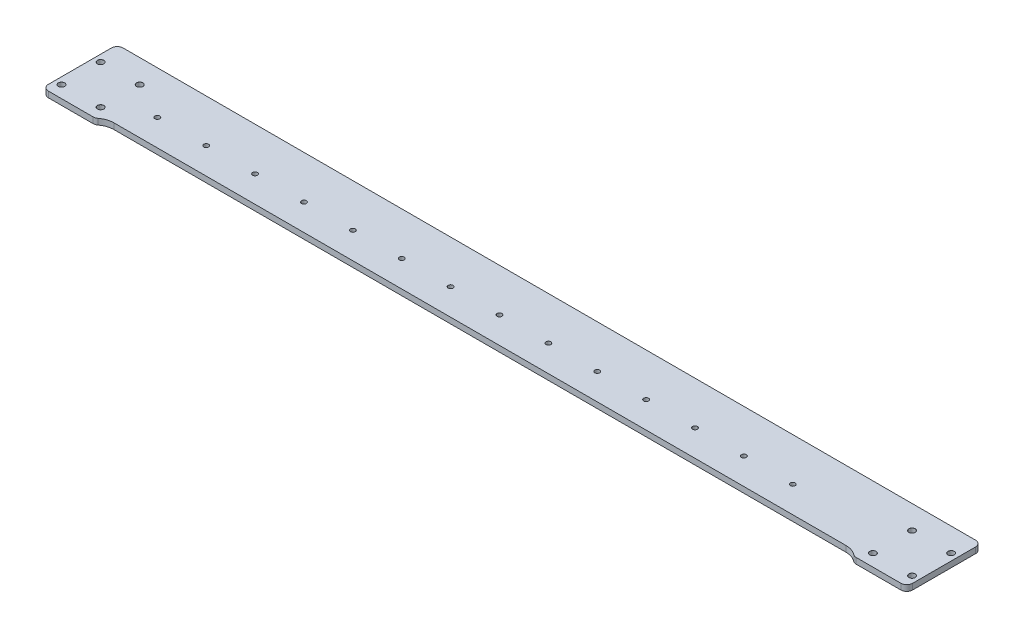
SolidWorks part; units mm, degrees
material "AISI 1045 Steel, cold drawn"
ref_plane "Front Plane" through (0, 0, 0) normal (0, 0, 1) x (1, 0, 0)
ref_plane "Top Plane" through (0, 0, 0) normal (0, 1, 0) x (1, 0, 0)
ref_plane "Right Plane" through (0, 0, 0) normal (1, 0, 0) x (0, 0, -1)
sketch "Sketch1" plane through (0, 0, 0) normal (0, 1, 0) x (1, 0, 0)
  line L0 (0, 0) -> (194, 0)
  line L1 (194, 0) -> (194, -2.7)
  line L2 (194, -2.7) -> (221, -2.7)
  line L3 (221, -2.7) -> (221, 29.7)
  line L4 (221, 29.7) -> (0, 29.7) construction
  line L7 (0, 0) -> (0, 29.7)
  line L8 (221, 13.5) -> (0, 13.5) construction
  line L9 (221, 29.7) -> (221, 35.5)
  line L10 (221, 35.5) -> (0, 35.5)
  line L11 (0, 35.5) -> (0, 29.7)
  dimension "D1" = 194
  dimension "D2" = 27
  dimension "D3" = 29.7
  dimension "D4" = 32.4
  dimension "D5" = 22
extrude "Boss-Extrude1" add sketch "Sketch1" along normal blind 3
hole_wizard "M3 Clearance Hole1" positions "Sketch2" profile "Sketch3" hole size "M3" standard "ANSI Metric" end condition through all
sketch "Sketch2" plane through (0, 3, 0) normal (0, 1, 0) x (1, 0, 0)
  line L1 (217.5, 3.5) -> (197.5, 3.5)
  line L2 (217.5, 3.5) -> (217.5, 23.5)
  line L3 (217.5, 23.5) -> (197.5, 23.5)
  line L4 (197.5, 3.5) -> (197.5, 23.5)
  line L5 (217.5, 3.5) -> (197.5, 23.5) construction
  line L6 (217.5, 23.5) -> (197.5, 3.5) construction
  line L10 (207.5, 13.5) -> (207.5, -2.7) construction
  line L13 (194, -2.7) -> (221, -2.7) construction
  line L17 (0, 0) -> (194, 0) construction
  point P2 (197.5, 23.5)
  point P35 (217.5, 3.5)
  point P36 (217.5, 23.5)
  point P37 (197.5, 3.5)
  dimension "D1" = 20
  dimension "D2" = 13.5
sketch "Sketch3" plane through (197.5, 3, -23.5) normal (1, 0, 0) x (0, 0, 1)
  line L0 (0, 0) -> (0, 3)
  line L1 (0, 3) -> (1.6, 3)
  line L2 (1.6, 3) -> (1.6, 0.025)
  line L3 (1.6, 0.025) -> (1.625, 0)
  line L5 (1.625, 0) -> (0, 0)
  line L6 (-1.6, 0.025) -> (-1.625, 0) construction
  line L11 (0, -6.35) -> (0, 107.95) construction
  dimension "Thru Hole Dia." = 3.2
  dimension "Thru Hole Depth" = 3
  dimension "Near C'Sink Dia." = 3.25
  dimension "Near C'Sink Angle" = 90
fillet "Fillet1" radius 10 1 edges at (194, 1.5, 0)
fillet "Fillet2" radius 3 3 edges at (221, 1.5, 2.7) (194, 1.5, 2.7) (221, 1.5, -35.5)
mirror "Mirror1" about plane through (0, 3, -35.5) normal (1, 0, 0) of bodies 103
hole_wizard "Tap Drill for M3x0.5 Tap2" positions "Sketch6" profile "Sketch7" hole size "M3x0.5" standard "ANSI Metric" end condition through all
sketch "Sketch6" plane through (0, 0, 0) normal (0, -1, 0) x (-1, 0, 0)
  line L0 (187.1655, 0) -> (-187.1655, 0) construction
  line L2 (221, 0.3) -> (221, 32.5) construction
  point P11 (178.5, 13.5)
  point P14 (0, 0)
  point P15 (0, 0)
  point P20 (0, 0)
  dimension "D1" = 13.5
  dimension "D2" = 42.5
sketch "Sketch7" plane through (-178.5, 0, -13.5) normal (1, 0, 0) x (0, 0, -1)
  line L0 (0, 0) -> (0, 3)
  line L1 (0, 3) -> (1.25, 3)
  line L2 (1.25, 3) -> (1.25, 0.025)
  line L3 (1.25, 0.025) -> (1.275, 0)
  line L5 (1.275, 0) -> (0, 0)
  line L6 (-1.25, 0.025) -> (-1.275, 0) construction
  line L11 (0, -6.35) -> (0, 107.95) construction
  dimension "Thru Hole Dia." = 2.5
  dimension "Thru Hole Depth" = 3
  dimension "Near C'Sink Dia." = 2.55
  dimension "Near C'Sink Angle" = 90
pattern_linear "LPattern1" count 14 spacing 25 along (1, 0, 0) of "Tap Drill for M3x0.5 Tap2"
